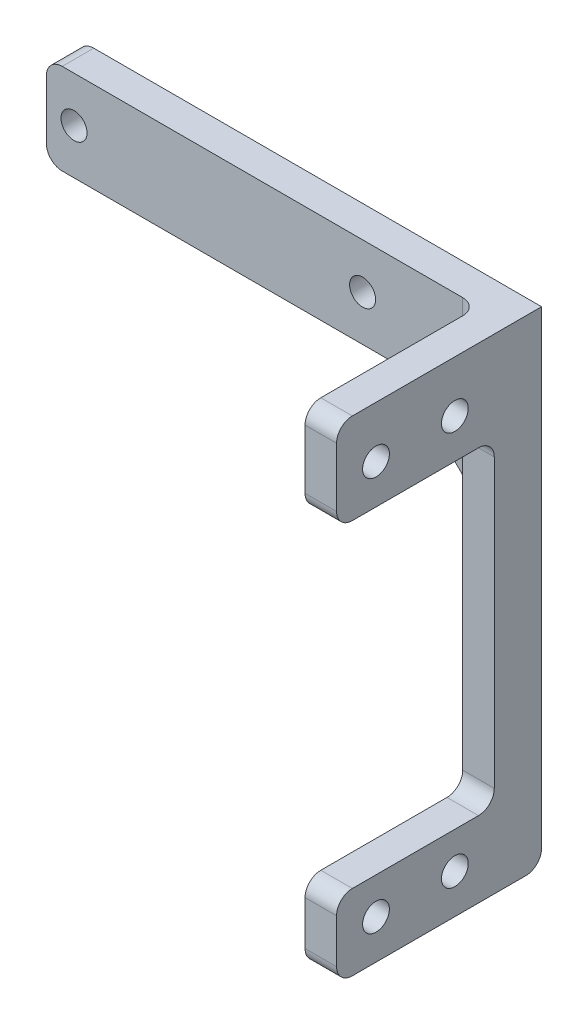
SolidWorks part; units mm, degrees
ref_plane "Front Plane" through (0, 0, 0) normal (0, 0, 1) x (1, 0, 0)
ref_plane "Top Plane" through (0, 0, 0) normal (0, 1, 0) x (1, 0, 0)
ref_plane "Right Plane" through (0, 0, 0) normal (1, 0, 0) x (0, 0, -1)
sketch "Sketch1" plane through (0, 0, 0) normal (0, 1, 0) x (1, 0, 0)
  line L1 (0, 0) -> (58.8, 0)
  line L2 (0, 0) -> (0, -4)
  line L3 (0, -4) -> (58.8, -4)
  line L4 (58.8, 0) -> (58.8, -4)
  line L5 (58.8, -4) -> (54.8, -4)
  line L6 (58.8, -4) -> (58.8, -26)
  line L7 (58.8, -26) -> (54.8, -26)
  line L8 (54.8, -4) -> (54.8, -26)
  dimension "D1" = 4
  dimension "D2" = 58.8
  dimension "D3" = 22
  dimension "D4" = 4
extrude "Boss-Extrude1" add sketch "Sketch1" along normal blind 11.5 contours L4 L1 L2 L3 | L5 L8 L7 L6 region at (29.4, 0, 2)
sketch "Sketch2" plane through (0, 0, 0) normal (0, 0, -1) x (-1, 0, 0)
  line L0 (0, 11.5) -> (0, 0) construction
  line L1 (0, 11.5) -> (-58.8, 11.5) construction
  circle A0 centre (-3.5, 5.75) radius 1.65
  circle A2 centre (-40.1, 5.75) radius 1.65
  point P4 (0, 5.75)
  dimension "D1" = 3.3
  dimension "D5" = 3.3
  dimension "D2" = 3.5
  dimension "D3" = 5.75
  dimension "D6" = 36.6
extrude "Cut-Extrude1" cut sketch "Sketch2" against normal up to next
sketch "Sketch3" plane through (0, 0, 0) normal (0, -1, 0) x (1, 0, 0)
  line L1 (54.8, 26) -> (58.8, 26)
  line L2 (54.8, 26) -> (54.8, 0)
  line L3 (54.8, 0) -> (58.8, 0)
  line L4 (58.8, 26) -> (58.8, 0)
extrude "Boss-Extrude2" add sketch "Sketch3" along normal blind 50
sketch "Sketch4" plane through (54.8, 0, 0) normal (-1, 0, 0) x (0, 0, 1)
  line L0 (26, 11.5) -> (26, -50) construction
  line L1 (26, 0) -> (6, 0)
  line L2 (26, 0) -> (26, -40.4)
  line L3 (26, -40.4) -> (6, -40.4)
  line L4 (6, 0) -> (6, -40.4)
  circle A0 centre (11, 5) radius 1.7
  circle A1 centre (21, 5) radius 1.7
  circle A2 centre (21, -45) radius 1.7
  circle A3 centre (11, -45) radius 1.7
  dimension "D3" = 3.4
  dimension "D1" = 20
  dimension "D2" = 40.4
  dimension "D4" = 5
  dimension "D5" = 5
  dimension "D6" = 2
  dimension "D7" = 2
extrude "Cut-Extrude2" cut sketch "Sketch4" against normal up to next
chamfer "Chamfer1" distance 10 angle 45 1 edges at (54.8, 0, 2)
fillet "Fillet1" radius 2 1 edges at (54.8, 0.75, 4)
fillet "Fillet2" radius 2 8 edges at (56.8, -50, 26) (56.8, -40.4, 26) (56.8, 0, 26) (56.8, 11.5, 26) (54.8, -10, 3) (44.8, 0, 2) (0, 11.5, 2) (0, 0, 2)
fillet "Fillet3" radius 2 2 edges at (56.8, 0, 6) (56.8, -40.4, 6)
fillet "Fillet4" radius 2 1 edges at (56.8, -50, 0)
